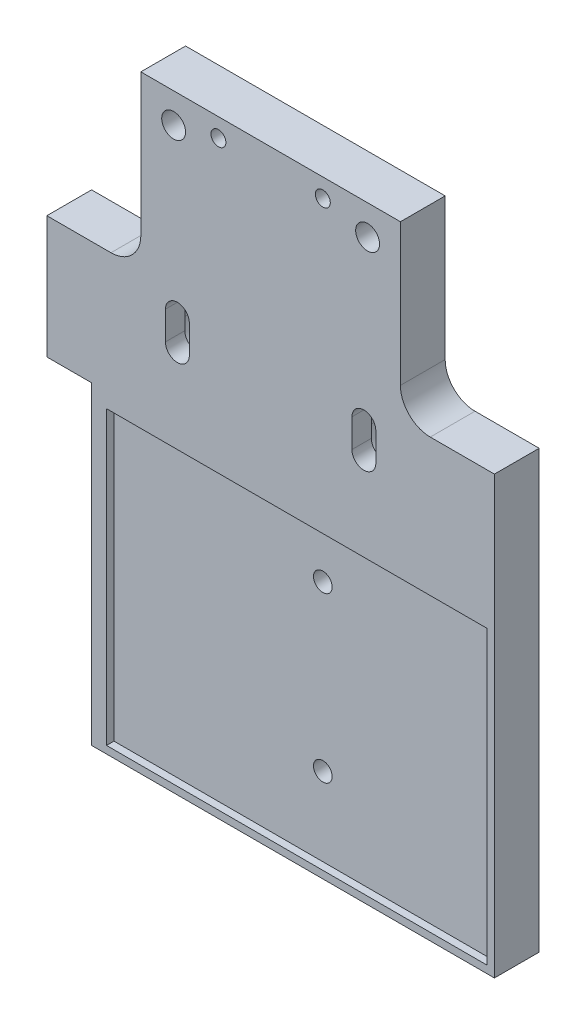
SolidWorks part; units mm, degrees
ref_plane "Front Plane" through (0, 0, 0) normal (0, 0, 1) x (1, 0, 0)
ref_plane "Top Plane" through (0, 0, 0) normal (0, 1, 0) x (1, 0, 0)
ref_plane "Right Plane" through (0, 0, 0) normal (1, 0, 0) x (0, 0, -1)
sketch "Sketch1" plane through (0, 0, 0) normal (0, 1, 0) x (1, 0, 0)
  line L1 (0, 0) -> (60, 0)
  line L2 (0, 0) -> (0, 6)
  line L3 (0, 6) -> (60, 6)
  line L4 (60, 0) -> (60, 6)
  dimension "D1" = 6
  dimension "D2" = 60
extrude "Boss-Extrude1" add sketch "Sketch1" along normal blind 81.5
sketch "Sketch2" plane through (0, 0, 0) normal (0, 0, 1) x (1, 0, 0)
  line L0 (30, 81.5) -> (30, 0) construction
  line L1 (0, 81.5) -> (60, 81.5) construction
  line L2 (0, 0) -> (60, 0) construction
  circle A0 centre (17, 77.5) radius 1.6
  circle A1 centre (43, 77.5) radius 1.6
  point P10 (0, 0)
  point P11 (0, 0)
  dimension "D3" = 3.2
  dimension "D1" = 4
  dimension "D2" = 26
extrude "Cut-Extrude1" cut sketch "Sketch2" against normal through all
sketch "Sketch3" plane through (0, 0, 0) normal (0, 0, 1) x (1, 0, 0)
  line L0 (30, 81.5) -> (30, 0) construction
  line L1 (0, 81.5) -> (60, 81.5) construction
  line L2 (0, 0) -> (60, 0) construction
  circle A0 centre (23, 79) radius 1
  circle A1 centre (37, 79) radius 1
  dimension "D5" = 2
  dimension "D1" = 7
  dimension "D2" = 7
  dimension "D3" = 2.5
  dimension "D4" = 2.5
extrude "Cut-Extrude2" cut sketch "Sketch3" against normal blind 4
hole_wizard "CBORE SLOT for M3 Hex Socket Head Cap Screw1" positions "Sketch4" profile "Sketch6" size "M3" standard "DIN" slot yes end condition through all
sketch "Sketch4" plane through (0, 0, -6) normal (0, 0, -1) x (-1, 0, 0)
  line L0 (-42.5, 50.2) -> (-42.5, 57.2) construction
  line L4 (-60, 81.5) -> (0, 81.5) construction
  line L5 (-30, 0) -> (-30, 81.5) construction
  line L6 (-60, 0) -> (0, 0) construction
  circle A0 centre (-17, 77.5) radius 1.6 construction
  point P0 (-42.5, 53.7)
  point P4 (-17.5, 53.7)
  point P23 (0, 0)
  point P24 (0, 0)
  dimension "D1" = 7
  dimension "D2" = 25
  dimension "D4" = 23.8
sketch "Sketch6" plane through (42.5, 53.7, -6) normal (1, 0, 0) x (0, 1, 0)
  line L0 (0, 0) -> (0, 6)
  line L1 (0, 6) -> (1.6, 6)
  line L3 (1.6, 6) -> (1.6, 3.4)
  line L4 (1.6, 3.4) -> (3.25, 3.4)
  line L5 (3.25, 3.4) -> (3.25, 0)
  line L7 (3.25, 0) -> (0, 0)
  line L11 (0, -6.35) -> (0, 107.95) construction
  dimension "Thru Hole Dia." = 3.2
  dimension "Thru Hole Depth" = 6
  dimension "C'Bore Dia." = 6.5
  dimension "C'Bore Depth" = 3.4
ref_plane "Plane1" through (30, 0, 0) normal (1, 0, 0) x (0, 0, -1)
sketch "Sketch8" plane through (0, 0, -6) normal (0, 0, -1) x (-1, 0, 0)
  line L0 (-60, 22.5) -> (0, 22.5) construction
  line L1 (-60, 81.5) -> (-60, 0) construction
  line L2 (0, 81.5) -> (0, 0) construction
  line L3 (-60, 0) -> (0, 0) construction
  circle A0 centre (-36, 11.5) radius 1.25
  circle A2 centre (-36, 33.5) radius 1.25
  dimension "D3" = 2.5
  dimension "D1" = 22.5
  dimension "D4" = 11
  dimension "D5" = 24
extrude "Cut-Extrude4" cut sketch "Sketch8" against normal through all
sketch "Sketch9" plane through (0, 0, 0) normal (0, -1, 0) x (-1, 0, 0)
  line L0 (-20, 4.5) -> (-6, 4.5)
  line L2 (0, 6) -> (0, 0) construction
  line L3 (-20, 6) -> (-20, 4.5)
  line L4 (-60, 6) -> (0, 6) construction
  line L7 (0, 6) -> (-20, 6)
  line L8 (-6, 0) -> (-6, 4.5)
  line L9 (0, 0) -> (-60, 0) construction
  line L10 (-6, 0) -> (0, 0)
  line L11 (0, 0) -> (0, 6)
  dimension "D1" = 20
  dimension "D2" = 6
  dimension "D3" = 1.5
extrude "Cut-Extrude5" cut sketch "Sketch9" against normal blind 42.1 and the other way through all
sketch "Sketch10" plane through (0, 0, 0) normal (0, 0, 1) x (1, 0, 0)
  line L1 (59, 1) -> (8, 1)
  line L2 (59, 1) -> (59, 40.1)
  line L3 (59, 40.1) -> (8, 40.1)
  line L4 (8, 1) -> (8, 40.1)
  line L5 (59, 1) -> (8, 40.1) construction
  line L6 (59, 40.1) -> (8, 1) construction
  line L7 (6, 0) -> (60, 0) construction
  line L8 (60, 81.5) -> (60, 0) construction
  point P0 (33.5, 20.55)
  dimension "D1" = 1
  dimension "D2" = 39.1
  dimension "D3" = 51
  dimension "D4" = 1
extrude "Cut-Extrude6" cut sketch "Sketch10" against normal blind 1
sketch "Sketch11" plane through (0, 0, -6) normal (0, 0, -1) x (-1, 0, 0)
  line L1 (-60, 81.5) -> (0, 81.5) construction
  line L4 (-30, 81.5) -> (-30, 0) construction
  line L5 (-60, 0) -> (-20, 0) construction
  line L6 (-60, 81.5) -> (-47.4, 81.5)
  line L8 (-60, 81.5) -> (-60, 58.5)
  line L9 (-60, 58.5) -> (-51.4, 58.5)
  line L10 (-47.4, 81.5) -> (-47.4, 62.5)
  line L11 (0, 81.5) -> (-12.6, 81.5)
  line L12 (0, 81.5) -> (0, 58.5)
  line L13 (0, 58.5) -> (-8.6, 58.5)
  line L14 (-12.6, 81.5) -> (-12.6, 62.5)
  arc A0 (-8.6, 58.5) -> (-12.6, 62.5) centre (-8.6, 62.5) cw
  arc A1 (-51.4, 58.5) -> (-47.4, 62.5) centre (-51.4, 62.5) ccw
  dimension "D4" = 4
  dimension "D1" = 23
  dimension "D2" = 23
  dimension "D3" = 34.8
extrude "Cut-Extrude7" cut sketch "Sketch11" against normal up to next
